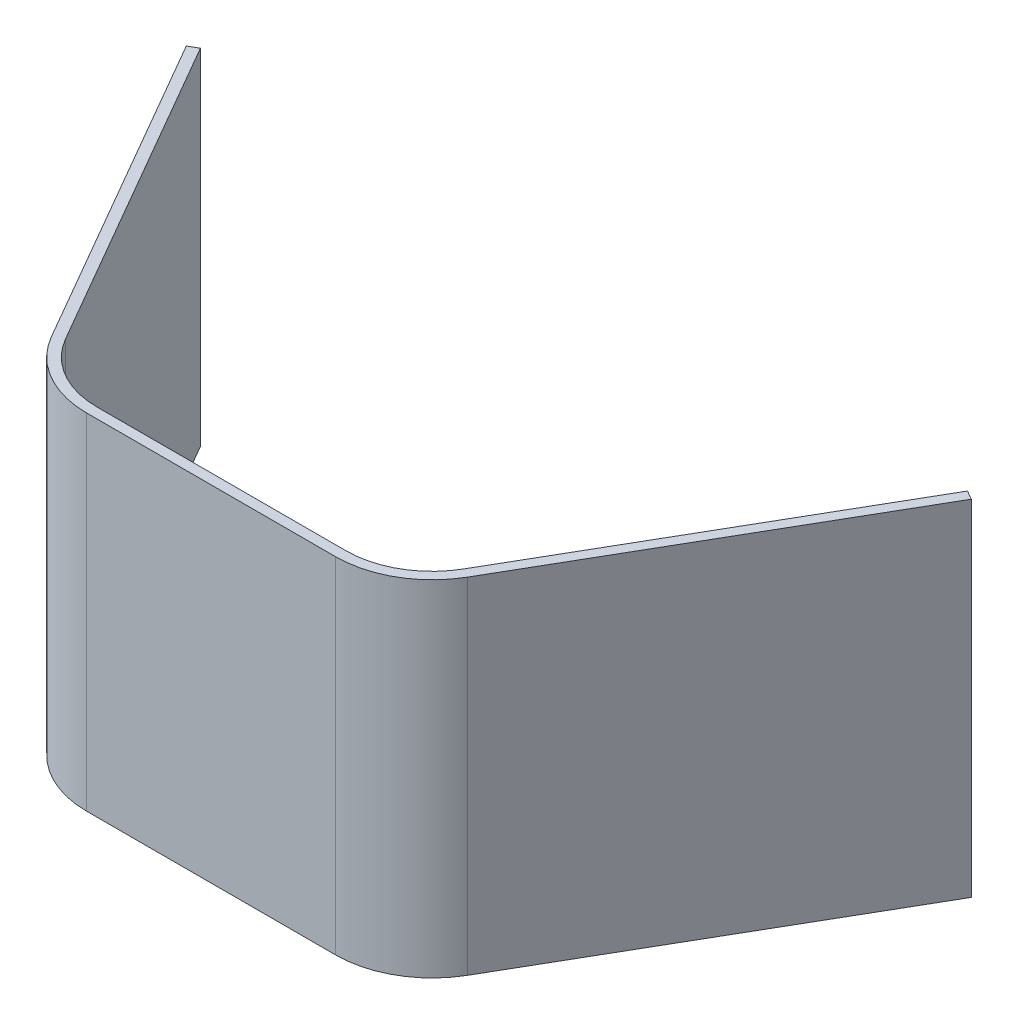
SolidWorks part; units mm, degrees
ref_plane "Plan de face" through (0, 0, 0) normal (0, 0, 1) x (1, 0, 0)
ref_plane "Plan de dessus" through (0, 0, 0) normal (0, 1, 0) x (1, 0, 0)
ref_plane "Plan de droite" through (0, 0, 0) normal (1, 0, 0) x (0, 0, -1)
sketch "Esquisse1" plane through (0, 0, 0) normal (0, 1, 0) x (1, 0, 0)
  line L0 (-45.5186, 77.6406) -> (-24.1332, 40.6)
  line L1 (-14.4338, 35) -> (14.4338, 35)
  line L2 (24.1332, 40.6) -> (45.5186, 77.6406)
  line L3 (0, -13.8682) -> (0, 114.7954) construction
  line L4 (0, 0) -> (-60.2437, 104.3452) construction
  line L5 (-44.4794, 78.2406) -> (-23.094, 41.2)
  line L6 (-14.4338, 36.2) -> (14.4338, 36.2)
  line L7 (23.094, 41.2) -> (44.4794, 78.2406)
  line L8 (-45.5186, 77.6406) -> (-44.4794, 78.2406)
  line L9 (45.5186, 77.6406) -> (44.4794, 78.2406)
  line L10 (-20.2073, 36.2) -> (20.2073, 36.2) construction
  line L11 (20.2073, 36.2) -> (44.4794, 78.2406) construction
  line L12 (-44.4794, 78.2406) -> (-20.2073, 36.2) construction
  line L13 (-20.9001, 35) -> (20.9001, 35) construction
  line L14 (20.9001, 35) -> (45.5186, 77.6406) construction
  line L15 (-45.5186, 77.6406) -> (-20.9001, 35) construction
  arc A0 (14.4338, 36.2) -> (23.094, 41.2) centre (14.4338, 46.2) ccw
  arc A1 (-23.094, 41.2) -> (-14.4338, 36.2) centre (-14.4338, 46.2) ccw
  arc A2 (14.4338, 35) -> (24.1332, 40.6) centre (14.4338, 46.2) ccw
  arc A3 (-24.1332, 40.6) -> (-14.4338, 35) centre (-14.4338, 46.2) ccw
  dimension "D5" = 10
  dimension "D6" = 11.2
  dimension "D1" = 30
  dimension "D3" = 35
  dimension "D4" = 90
  dimension "D2" = 1.2
extrude "Boss.-Extru.1" add sketch "Esquisse1" along normal blind 40
